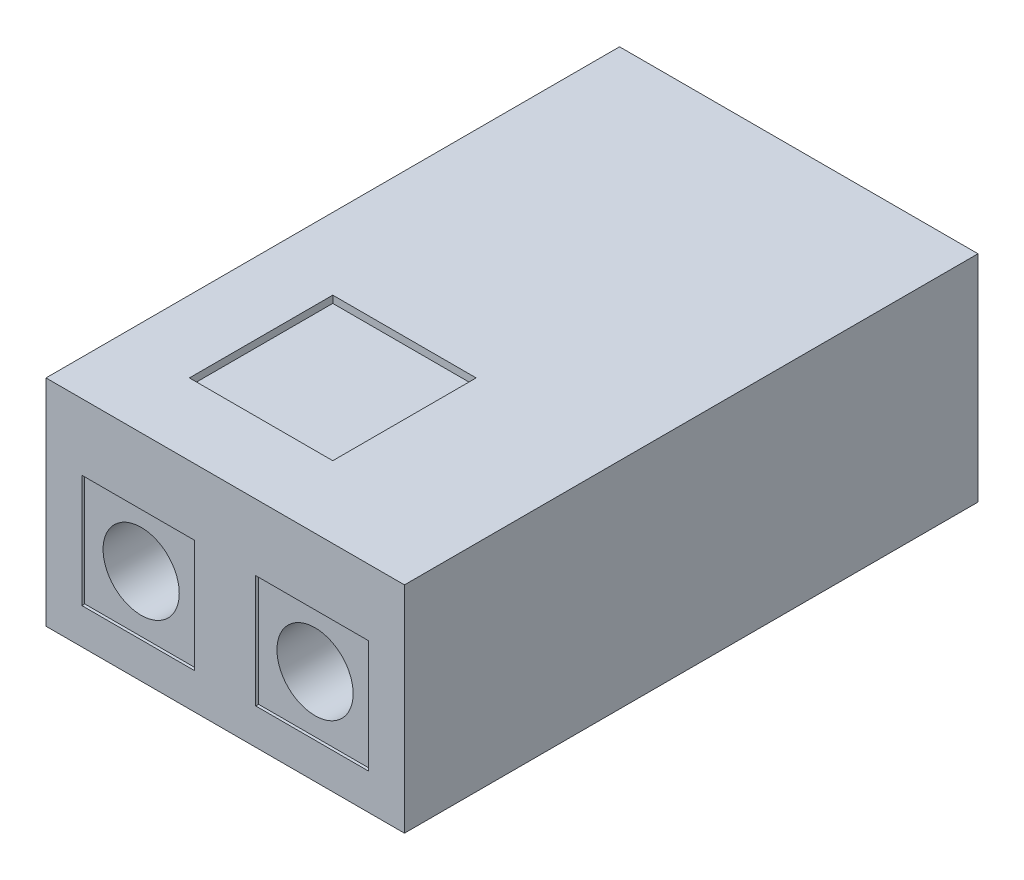
SolidWorks part; units mm, degrees
ref_plane "Front Plane" through (0, 0, 0) normal (0, 0, 1) x (1, 0, 0)
ref_plane "Top Plane" through (0, 0, 0) normal (0, 1, 0) x (1, 0, 0)
ref_plane "Right Plane" through (0, 0, 0) normal (1, 0, 0) x (0, 0, -1)
sketch "Sketch1" plane through (0, 0, 0) normal (0, 1, 0) x (1, 0, 0)
  line L1 (-46.3939, 60.5194) -> (17.1061, 60.5194)
  line L2 (-46.3939, 60.5194) -> (-46.3939, -41.0806)
  line L3 (-46.3939, -41.0806) -> (17.1061, -41.0806)
  line L4 (17.1061, 60.5194) -> (17.1061, -41.0806)
  dimension "D1" = 63.5
  dimension "D2" = 101.6
extrude "Boss-Extrude1" add sketch "Sketch1" along normal blind 38.1
sketch "Sketch2" plane through (0, 0, 41.0806) normal (0, 0, 1) x (1, 0, 0)
  line L0 (-46.3939, 6.35) -> (17.1061, 6.35)
  line L1 (-46.3939, 38.1) -> (-46.3939, 0) construction
  line L2 (17.1061, 38.1) -> (17.1061, 0) construction
  line L3 (-46.3939, 0) -> (17.1061, 0) construction
  line L4 (-40.0439, 6.35) -> (-20.0439, 6.35)
  line L5 (-40.0439, 6.35) -> (-40.0439, 26.35)
  line L6 (-40.0439, 26.35) -> (-20.0439, 26.35)
  line L7 (-20.0439, 6.35) -> (-20.0439, 26.35)
  line L8 (-9.2439, 6.35) -> (10.7561, 6.35)
  line L9 (-9.2439, 6.35) -> (-9.2439, 26.35)
  line L10 (-9.2439, 26.35) -> (10.7561, 26.35)
  line L11 (10.7561, 6.35) -> (10.7561, 26.35)
  line L12 (-30.0439, 26.35) -> (-30.0439, 6.35)
  line L13 (0.7561, 26.35) -> (0.7561, 6.35)
  circle A0 centre (-30.0439, 16.35) radius 6.75
  circle A1 centre (0.7561, 16.35) radius 6.75
  dimension "D8" = 13.5
  dimension "D9" = 13.5
  dimension "D1" = 20
  dimension "D2" = 20
  dimension "D3" = 20
  dimension "D4" = 20
  dimension "D5" = 6.35
  dimension "D6" = 6.35
  dimension "D7" = 6.35
extrude "Cut-Extrude1" cut sketch "Sketch2" against normal blind 38.1 contours L12 A0 | L12 A0 | L13 A1 | L13 A1 region at (-32.9087, 16.35, 41.0806) region at (-27.1791, 16.35, 41.0806) region at (-2.1087, 16.35, 41.0806) region at (3.6209, 16.35, 41.0806)
extrude "Cut-Extrude2" cut sketch "Sketch2<3>" against normal blind 0.508 contours A0 L12 L6 L5 L0 | A0 L12 L4 L7 L6 | A1 L13 L10 L9 L0 | A1 L13 L8 L11 L10 region at (-39.8203, 16.35, 41.0806) region at (-9.0203, 16.35, 41.0806) region at (-29.8203, 7.975, 41.0806) region at (0.9797, 7.975, 41.0806)
sketch "Sketch2<3>" plane through (0, 0, 41.0806) normal (0, 0, 1) x (1, 0, 0) same geometry as "Sketch2"
sketch "Sketch3" plane through (0, 0, -60.5194) normal (0, 0, -1) x (-1, 0, 0)
  line L0 (-17.1061, 0) -> (46.3939, 0) construction
  line L1 (23.5339, 25.4) -> (33.6939, 25.4)
  line L2 (23.5339, 25.4) -> (23.5339, 19.05)
  line L3 (23.5339, 19.05) -> (33.6939, 19.05)
  line L4 (33.6939, 25.4) -> (33.6939, 19.05)
  line L5 (-10.7561, 12.7) -> (1.9439, 12.7)
  line L6 (-10.7561, 12.7) -> (-10.7561, 6.35)
  line L7 (-10.7561, 6.35) -> (1.9439, 6.35)
  line L8 (1.9439, 12.7) -> (1.9439, 6.35)
  line L9 (46.3939, 38.1) -> (46.3939, 0) construction
  line L10 (-17.1061, 38.1) -> (-17.1061, 0) construction
  circle A0 centre (13.3739, 12.7) radius 3.81
  dimension "D5" = 7.62
  dimension "D1" = 10.16
  dimension "D2" = 6.35
  dimension "D3" = 19.05
  dimension "D4" = 12.7
  dimension "D6" = 12.7
  dimension "D7" = 33.02
  dimension "D8" = 12.7
  dimension "D9" = 6.35
  dimension "D10" = 6.35
  dimension "D11" = 6.35
extrude "Cut-Extrude3" cut sketch "Sketch3" against normal blind 9.525 contours L6 L5 L8 L7 | L2 L1 L4 L3 | A0
sketch "Sketch5" plane through (0, 38.1, 0) normal (0, 1, 0) x (1, 0, 0)
  line L0 (-46.3939, -41.0806) -> (17.1061, -41.0806) construction
  line L1 (-8.2939, -2.9806) -> (-33.6939, -2.9806)
  line L2 (-8.2939, -2.9806) -> (-8.2939, -28.3806)
  line L3 (-8.2939, -28.3806) -> (-33.6939, -28.3806)
  line L4 (-33.6939, -2.9806) -> (-33.6939, -28.3806)
  line L5 (-46.3939, 60.5194) -> (-46.3939, -41.0806) construction
  dimension "D1" = 25.4
  dimension "D2" = 25.4
  dimension "D3" = 12.7
  dimension "D4" = 12.7
extrude "Cut-Extrude4" cut sketch "Sketch5" against normal blind 1.27
